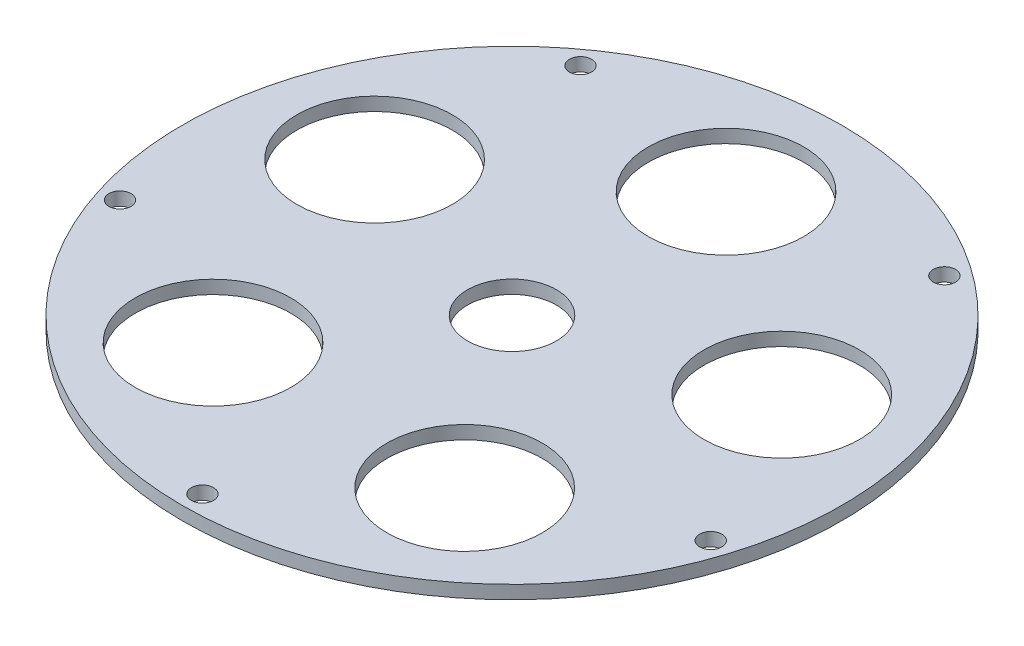
SolidWorks part; units mm, degrees
ref_plane "Front Plane" through (0, 0, 0) normal (0, 0, 1) x (1, 0, 0)
ref_plane "Top Plane" through (0, 0, 0) normal (0, 1, 0) x (1, 0, 0)
ref_plane "Right Plane" through (0, 0, 0) normal (1, 0, 0) x (0, 0, -1)
sketch "Sketch1" plane through (0, 0, 0) normal (0, 1, 0) x (1, 0, 0)
  line L0 (0, 0) -> (0, 74.1827) construction
  line L1 (70.5519, 22.9237) -> (0, 0) construction
  line L2 (0, 0) -> (43.6035, -60.015) construction
  line L3 (-43.6035, -60.015) -> (0, 0) construction
  line L4 (0, 0) -> (-70.5519, 22.9237) construction
  line L5 (-45.8244, 14.8893) -> (-28.3211, -38.9806) construction
  line L6 (-43.6035, 60.015) -> (0, 0) construction
  line L7 (0, 0) -> (43.6035, 60.015) construction
  line L8 (70.5519, -22.9237) -> (0, 0) construction
  line L9 (0, 0) -> (0, -74.1827) construction
  line L10 (-70.5519, -22.9237) -> (0, 0) construction
  circle A0 centre (0, 0) radius 74.1827
  circle A1 centre (0, 48.1827) radius 17.5
  circle A2 centre (45.8244, 14.8893) radius 17.5
  circle A3 centre (28.3211, -38.9806) radius 17.5
  circle A4 centre (-28.3211, -38.9806) radius 17.5
  circle A5 centre (-45.8244, 14.8893) radius 17.5
  circle A6 centre (0, 0) radius 10
  circle A7 centre (40.9584, 56.3745) radius 2.5
  circle A8 centre (66.2722, -21.5331) radius 2.5
  circle A9 centre (0, -69.6827) radius 2.5
  circle A10 centre (-66.605, -21.6413) radius 2.5
  circle A11 centre (-40.9584, 56.3745) radius 2.5
  dimension "D1" = 72
  dimension "D5" = 35
  dimension "D6" = 35
  dimension "D7" = 35
  dimension "D8" = 35
  dimension "D9" = 35
  dimension "D16" = 20
  dimension "D21" = 5
  dimension "D22" = 5
  dimension "D23" = 5
  dimension "D24" = 5
  dimension "D25" = 5
  dimension "D2" = 72
  dimension "D3" = 72
  dimension "D4" = 72
  dimension "D10" = 26
  dimension "D11" = 26
  dimension "D12" = 26
  dimension "D13" = 26
  dimension "D14" = 26
  dimension "D15" = 48.1827
  dimension "D17" = 36
  dimension "D18" = 36
  dimension "D19" = 36
  dimension "D20" = 36
  dimension "D26" = 4.5
  dimension "D27" = 4.5
  dimension "D28" = 4.5
  dimension "D29" = 4.5
  dimension "D30" = 4.15
extrude "Boss-Extrude2" add sketch "Sketch1" against normal blind 3 contours A0
extrude "Cut-Extrude1" cut sketch "Sketch1<4>" against normal blind 4 contours A4 | A3 | A2 | A1 | A6 | A5
sketch "Sketch1<4>" plane through (0, 0, 0) normal (0, 1, 0) x (1, 0, 0) same geometry as "Sketch1"
extrude "Cut-Extrude2" cut sketch "Sketch1<5>" against normal blind 4 contours A10 | A9 | A8 | A7 | A11
sketch "Sketch1<5>" plane through (0, 0, 0) normal (0, 1, 0) x (1, 0, 0) same geometry as "Sketch1"
